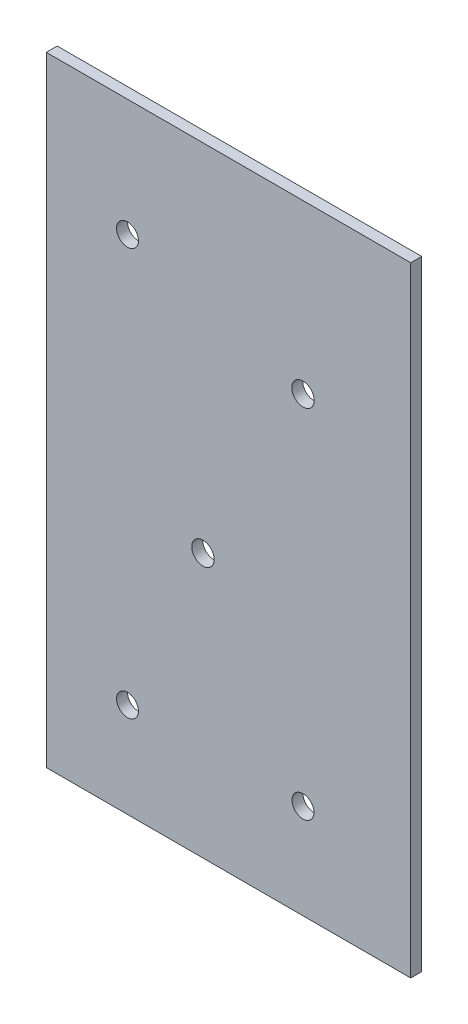
SolidWorks part; units mm, degrees
ref_plane "Front Plane" through (0, 0, 0) normal (0, 0, 1) x (1, 0, 0)
ref_plane "Top Plane" through (0, 0, 0) normal (0, 1, 0) x (1, 0, 0)
ref_plane "Right Plane" through (0, 0, 0) normal (1, 0, 0) x (0, 0, -1)
sketch "Sketch1" plane through (0, 0, 0) normal (0, 0, 1) x (1, 0, 0)
  line L0 (88.9, 95.25) -> (63.5, 95.25) construction
  line L1 (1.8891, 210.8161) -> (107.3869, 210.8161)
  line L2 (1.8891, 210.8161) -> (1.8891, 31.5173)
  line L3 (1.8891, 31.5173) -> (107.3869, 31.5173)
  line L4 (107.3869, 210.8161) -> (107.3869, 31.5173)
  line L5 (63.5, 95.25) -> (63.5, 146.05) construction
  line L8 (88.9, 95.25) -> (88.9, 146.05) construction
  circle A0 centre (25.4, 58.9643) radius 3.175
  circle A1 centre (76.2, 58.9643) radius 3.175
  circle A2 centre (25.4, 176.8929) radius 3.175
  circle A4 centre (76.2, 162.306) radius 3.2512
  circle A6 centre (47.244, 107.95) radius 3.2512
  dimension "D1" = 6.35
  dimension "D6" = 6.5024
  dimension "D4" = 16.256
  dimension "D7" = 33.9233
  dimension "D8" = 23.5109
  dimension "D9" = 27.447
  dimension "D10" = 31.1869
  dimension "D5" = 12.7
  dimension "D2" = 16.256
  dimension "D3" = 12.7
extrude "Boss-Extrude1" add sketch "Sketch1" along normal blind 3.175
equation "\"80/20 to Center Hole\"= .64in"
equation "\"80/20 from Edge\"= 0.5in"
equation "\"D5@Sketch1\"=\"80/20 from Edge\""
equation "\"D3@Sketch1\"=\"80/20 from Edge\""
equation "\"D4@Sketch1\"=\"80/20 to Center Hole\""
equation "\"D2@Sketch1\"=\"80/20 to Center Hole\""
